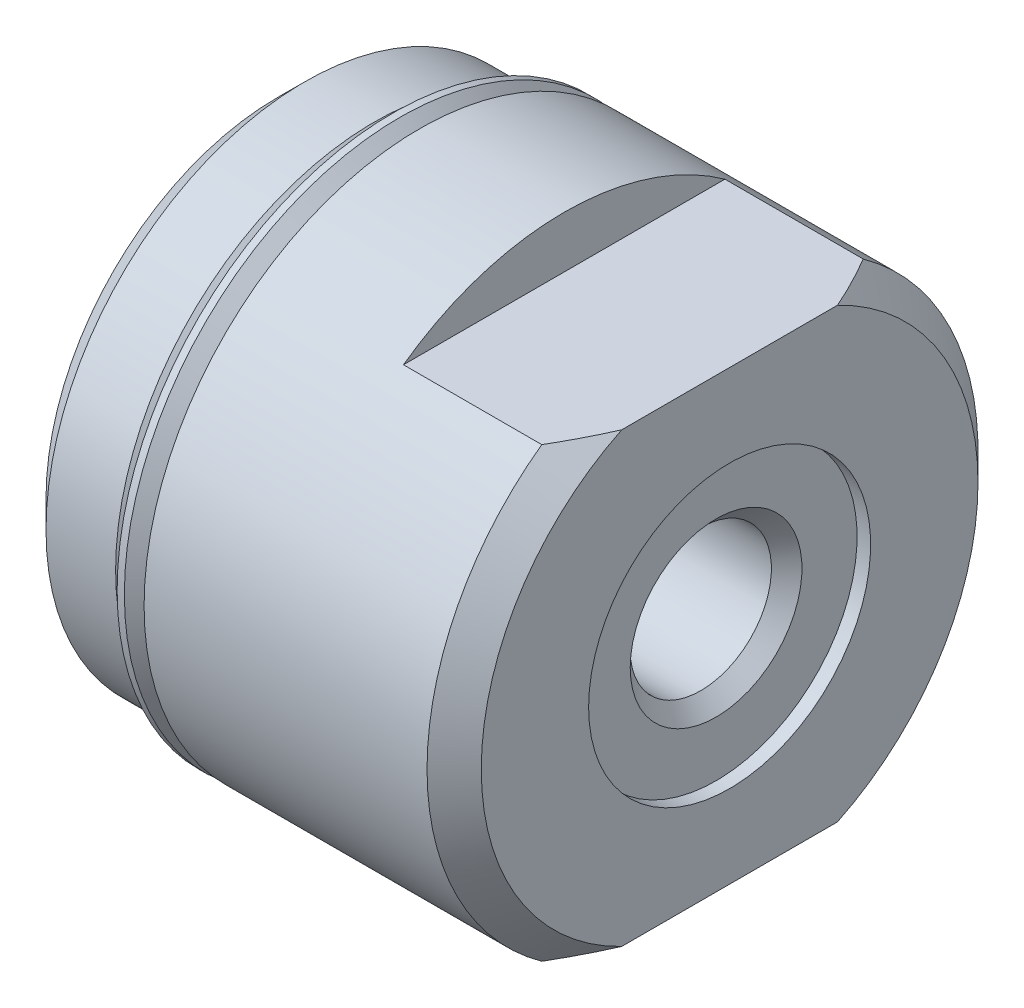
SolidWorks part; units mm, degrees
material "6061-T6 (SS)"
ref_plane "Front Plane" through (0, 0, 0) normal (0, 0, 1) x (1, 0, 0)
ref_plane "Top Plane" through (0, 0, 0) normal (0, 1, 0) x (1, 0, 0)
ref_plane "Right Plane" through (0, 0, 0) normal (1, 0, 0) x (0, 0, -1)
sketch "Sketch1" plane through (0, 0, 0) normal (0, 0, 1) x (1, 0, 0)
  line L0 (0, 0) -> (0, 6.5088)
  line L1 (0, 6.5088) -> (0.762, 7.2707)
  line L2 (0.762, 7.2707) -> (2.7178, 7.2707)
  line L3 (2.7178, 7.2707) -> (3.3528, 6.6357)
  line L4 (3.3528, 6.6357) -> (3.9878, 6.6357)
  line L5 (3.9878, 6.6357) -> (3.9878, 7.7406)
  line L6 (3.9878, 7.7406) -> (11.938, 7.7406)
  line L7 (11.938, 7.7406) -> (12.7, 6.9787)
  line L8 (12.7, 6.9787) -> (12.7, 0)
  line L9 (12.7, 0) -> (0, 0)
  line L10 (12.7, 0) -> (0, 0) construction
revolve "Revolve1" add sketch "Sketch1" angle 360 about L10 reverse direction yes
sketch "Sketch2" plane through (0, 0, 0) normal (0, 0, 1) x (1, 0, 0)
  line L0 (12.319, 0) -> (12.319, 3.9624)
  line L1 (12.319, 3.9624) -> (12.7, 3.9624)
  line L2 (12.7, 3.9624) -> (12.7, 0)
  line L3 (12.7, 0) -> (12.319, 0)
  line L4 (12.7, 0) -> (12.319, 0) construction
revolve "Cut-Revolve1" cut sketch "Sketch2" angle 360 about L4 reverse direction yes
sketch "Sketch3" plane through (0, 0, 0) normal (0, 0, 1) x (1, 0, 0)
  line L0 (0, 0) -> (0, 1.9837)
  line L1 (0, 1.9837) -> (11.8897, 1.9837)
  line L2 (11.8897, 1.9837) -> (12.319, 2.413)
  line L3 (12.319, 2.413) -> (12.319, 0)
  line L4 (12.319, 0) -> (0, 0)
  line L5 (12.319, 0) -> (0, 0) construction
revolve "Cut-Revolve2" cut sketch "Sketch3" angle 360 about L5 reverse direction yes
cosmetic thread "Cosmetic Thread1" parameters "D1"=5.08, "D2"=4.826
ref_plane "Plane1" through (12.7, 0, 0) normal (1, 0, 0) x (0, 0, -1)
sketch "Sketch4" plane through (12.7, 0, 0) normal (1, 0, 0) x (0, 0, -1)
  line L0 (-30.9626, -15.4813) -> (30.9626, -15.4813)
  line L1 (30.9626, -15.4813) -> (30.9626, 15.4813)
  line L2 (30.9626, 15.4813) -> (-30.9626, 15.4813)
  line L3 (-30.9626, 15.4813) -> (-30.9626, -15.4813)
  line L4 (-15.4813, -6.2865) -> (15.4813, -6.2865)
  line L5 (15.4813, -6.2865) -> (15.4813, 6.2865)
  line L6 (15.4813, 6.2865) -> (-15.4813, 6.2865)
  line L7 (-15.4813, 6.2865) -> (-15.4813, -6.2865)
extrude "Cut-Extrude1" cut sketch "Sketch4" against normal blind 4.6482
ref_plane "Plane2" through (13.5128, 0, 0) normal (1, 0, 0) x (0, 0, -1)
ref_plane "Plane3" through (0, 0, 0) normal (0, 0.9998, 0.0175) x (1, 0, 0)
ref_plane "Plane4" through (10.3124, 0, 0) normal (1, 0, 0) x (0, 0, -1)
ref_plane "Plane5" through (3.3528, 0, 0) normal (1, 0, 0) x (0, 0, -1)
sketch "Sketch5" plane through (0, 0, 0) normal (0, 0, 1) x (1, 0, 0)
  line L0 (3.2301, 7.7406) -> (3.2301, 7.6565)
  line L1 (3.2301, 7.6565) -> (3.8708, 7.0158)
  line L2 (3.8708, 6.8362) -> (3.6703, 6.6357)
  line L3 (3.6703, 6.6357) -> (3.3528, 6.6357)
  line L4 (3.3528, 6.6357) -> (3.3528, 6.3818)
  line L5 (3.3528, 6.3818) -> (3.9878, 6.3818)
  line L6 (3.9878, 6.3818) -> (3.9878, 7.1861)
  line L7 (3.9878, 7.1861) -> (3.4333, 7.7406)
  line L8 (3.4333, 7.7406) -> (3.2301, 7.7406)
  line L9 (3.9878, 0) -> (3.3528, 0) construction
  arc A0 (3.8708, 7.0158) -> (3.8708, 6.8362) centre (3.781, 6.926) cw
revolve "Revolve2" add sketch "Sketch5" angle 360 about L9 reverse direction yes
ref_plane "Plane6" through (12.827, 0, 0) normal (1, 0, 0) x (0, 0, -1)
ref_plane "Plane7" through (0, 0, 0) normal (1, 0, 0) x (0, 0, -1)
ref_plane "Plane8" through (8.0518, 0, 0) normal (1, 0, 0) x (0, 0, -1)
ref_plane "Plane9" through (12.7, 0, 0) normal (1, 0, 0) x (0, 0, -1)
ref_plane "Plane10" through (0, 0, 0) normal (0, 0, 1) x (1, 0, 0)
ref_plane "Plane11" through (0, 0, 0) normal (0, 1, 0) x (1, 0, 0)
ref_plane "Plane12" through (0, 0, 0) normal (0, 1, 0) x (1, 0, 0)
ref_plane "Plane13" through (13.5128, 0, 0) normal (1, 0, 0) x (0, 0, -1)
ref_plane "cut1 XY" through (12.7, 0, 0) normal (1, 0, 0) x (0, 0, -1)
ref_plane "cut1 XZ" through (0, 6.2865, 0) normal (0, -1, 0) x (-1, 0, 0)
ref_plane "cut1 YZ" through (0, 0, 0) normal (0, 0, -1) x (-1, 0, 0)
ref_axis "cut1 X" through (12.7, 6.2865, 80.9) along (0, 0, -1)
ref_axis "cut1 Y" through (12.7, -50, 0) along (0, 1, 0)
ref_axis "cut1 Z" through (80.9, 6.2865, 0) along (-1, 0, 0)
sketch3d "cut1"
  point P0 (12.7, 6.2865, 0)
ref_plane "cut2 XY" through (12.7, 0, 0) normal (1, 0, 0) x (0, 0, -1)
ref_plane "cut2 XZ" through (0, -6.2865, 0) normal (0, -1, 0) x (-1, 0, 0)
ref_plane "cut2 YZ" through (0, 0, 0) normal (0, 0, -1) x (-1, 0, 0)
ref_axis "cut2 X" through (12.7, -6.2865, 80.9) along (0, 0, -1)
ref_axis "cut2 Y" through (12.7, -50, 0) along (0, 1, 0)
ref_axis "cut2 Z" through (80.9, -6.2865, 0) along (-1, 0, 0)
sketch3d "cut2"
  point P0 (12.7, -6.2865, 0)
ref_plane "cutf1 XY" through (0, 0, 0) normal (0, 0, 1) x (1, 0, 0)
ref_plane "cutf1 XZ" through (0, 0, 0) normal (0, -1, 0) x (-1, 0, 0)
ref_plane "cutf1 YZ" through (12.7, 0, 0) normal (1, 0, 0) x (0, 0, -1)
ref_axis "cutf1 X" through (-80.9, 0, 0) along (1, 0, 0)
ref_axis "cutf1 Y" through (12.7, -50, 0) along (0, 1, 0)
ref_axis "cutf1 Z" through (12.7, 0, 80.9) along (0, 0, -1)
sketch3d "cutf1"
  point P0 (12.7, 0, 0)
ref_plane "cutf2 XY" through (0, 0, 0) normal (0, 0, 1) x (1, 0, 0)
ref_plane "cutf2 XZ" through (0, 0, 0) normal (0, -1, 0) x (-1, 0, 0)
ref_plane "cutf2 YZ" through (8.0518, 0, 0) normal (1, 0, 0) x (0, 0, -1)
ref_axis "cutf2 X" through (-80.9, 0, 0) along (1, 0, 0)
ref_axis "cutf2 Y" through (8.0518, -50, 0) along (0, 1, 0)
ref_axis "cutf2 Z" through (8.0518, 0, 80.9) along (0, 0, -1)
sketch3d "cutf2"
  point P0 (8.0518, 0, 0)
ref_plane "lovra XY" through (12.7, 0, 0) normal (1, 0, 0) x (0, 0, -1)
ref_plane "lovra XZ" through (0, 0, 0) normal (0, 0, -1) x (-1, 0, 0)
ref_plane "lovra YZ" through (0, 0, 0) normal (0, 1, 0) x (1, 0, 0)
ref_axis "lovra X" through (12.7, -50, 0) along (0, 1, 0)
ref_axis "lovra Y" through (12.7, 0, -80.9) along (0, 0, 1)
ref_axis "lovra Z" through (80.9, 0, 0) along (-1, 0, 0)
sketch3d "lovra"
  point P0 (12.7, 0, 0)
ref_plane "lovra1 XY" through (8.0518, 0, 0) normal (1, 0, 0) x (0, 0, -1)
ref_plane "lovra1 XZ" through (0, 0, 0) normal (0, -1, 0) x (-1, 0, 0)
ref_plane "lovra1 YZ" through (0, 0, 0) normal (0, 0, -1) x (-1, 0, 0)
ref_axis "lovra1 X" through (8.0518, 0, 80.9) along (0, 0, -1)
ref_axis "lovra1 Y" through (8.0518, -50, 0) along (0, 1, 0)
ref_axis "lovra1 Z" through (80.9, 0, 0) along (-1, 0, 0)
sketch3d "lovra1"
  point P0 (8.0518, 0, 0)
ref_plane "lovra2 XY" through (8.0518, 0, 0) normal (1, 0, 0) x (0, 0, -1)
ref_plane "lovra2 XZ" through (0, 6.2865, 0) normal (0, -1, 0) x (-1, 0, 0)
ref_plane "lovra2 YZ" through (0, 0, 0) normal (0, 0, -1) x (-1, 0, 0)
ref_axis "lovra2 X" through (8.0518, 6.2865, 80.9) along (0, 0, -1)
ref_axis "lovra2 Y" through (8.0518, -50, 0) along (0, 1, 0)
ref_axis "lovra2 Z" through (80.9, 6.2865, 0) along (-1, 0, 0)
sketch3d "lovra2"
  point P0 (8.0518, 6.2865, 0)
ref_plane "lovra21 XY" through (0, 0, 0) normal (1, 0, 0) x (0, 0, -1)
ref_plane "lovra21 XZ" through (0, 0, 0) normal (0, -1, 0) x (-1, 0, 0)
ref_plane "lovra21 YZ" through (0, 0, 5.2705) normal (0, 0, -1) x (-1, 0, 0)
ref_axis "lovra21 X" through (0, 0, 80.9) along (0, 0, -1)
ref_axis "lovra21 Y" through (0, -50, 5.2705) along (0, 1, 0)
ref_axis "lovra21 Z" through (80.9, 0, 5.2705) along (-1, 0, 0)
sketch3d "lovra21"
  point P0 (0, 0, 5.2705)
ref_plane "lovra22 XY" through (0, 0, 0) normal (1, 0, 0) x (0, 0, -1)
ref_plane "lovra22 XZ" through (0, 0, 0) normal (0, -1, 0) x (-1, 0, 0)
ref_plane "lovra22 YZ" through (0, 0, -5.2705) normal (0, 0, -1) x (-1, 0, 0)
ref_axis "lovra22 X" through (0, 0, 80.9) along (0, 0, -1)
ref_axis "lovra22 Y" through (0, -50, -5.2705) along (0, 1, 0)
ref_axis "lovra22 Z" through (80.9, 0, -5.2705) along (-1, 0, 0)
sketch3d "lovra22"
  point P0 (0, 0, -5.2705)
ref_plane "lovra3 XY" through (8.0518, 0, 0) normal (1, 0, 0) x (0, 0, -1)
ref_plane "lovra3 XZ" through (0, -6.2865, 0) normal (0, -1, 0) x (-1, 0, 0)
ref_plane "lovra3 YZ" through (0, 0, 0) normal (0, 0, -1) x (-1, 0, 0)
ref_axis "lovra3 X" through (8.0518, -6.2865, 80.9) along (0, 0, -1)
ref_axis "lovra3 Y" through (8.0518, -50, 0) along (0, 1, 0)
ref_axis "lovra3 Z" through (80.9, -6.2865, 0) along (-1, 0, 0)
sketch3d "lovra3"
  point P0 (8.0518, -6.2865, 0)
ref_plane "olen XY" through (12.7, 0, 0) normal (1, 0, 0) x (0, 0, -1)
ref_plane "olen XZ" through (0, 0, 0) normal (0, -1, 0) x (-1, 0, 0)
ref_plane "olen YZ" through (0, 0, 0) normal (0, 0, -1) x (-1, 0, 0)
ref_axis "olen X" through (12.7, 0, 80.9) along (0, 0, -1)
ref_axis "olen Y" through (12.7, -50, 0) along (0, 1, 0)
ref_axis "olen Z" through (80.9, 0, 0) along (-1, 0, 0)
sketch3d "olen"
  point P0 (12.7, 0, 0)
ref_plane "to_mounting_bracket XY" through (13.5128, 0, 0) normal (1, 0, 0) x (0, 0, -1)
ref_plane "to_mounting_bracket XZ" through (0, 0, 0) normal (0, -1, 0) x (-1, 0, 0)
ref_plane "to_mounting_bracket YZ" through (0, 0, 0) normal (0, 0, -1) x (-1, 0, 0)
ref_axis "to_mounting_bracket X" through (13.5128, 0, 80.9) along (0, 0, -1)
ref_axis "to_mounting_bracket Y" through (13.5128, -50, 0) along (0, 1, 0)
ref_axis "to_mounting_bracket Z" through (80.9, 0, 0) along (-1, 0, 0)
sketch3d "to_mounting_bracket"
  point P0 (13.5128, 0, 0)
ref_plane "to_nut XY" through (0, 0, 0) normal (1, 0, 0) x (0, 0, -1)
ref_plane "to_nut XZ" through (0, 0, 0) normal (0, -1, 0) x (-1, 0, 0)
ref_plane "to_nut YZ" through (0, 0, 0) normal (0, 0, -1) x (-1, 0, 0)
ref_axis "to_nut X" through (0, 0, 80.9) along (0, 0, -1)
ref_axis "to_nut Y" through (0, -50, 0) along (0, 1, 0)
ref_axis "to_nut Z" through (80.9, 0, 0) along (-1, 0, 0)
sketch3d "to_nut"
  point P0 (0, 0, 0)
ref_plane "to_pin XY" through (0, 0, 0) normal (0, 0, 1) x (1, 0, 0)
ref_plane "to_pin XZ" through (0, 0, 0) normal (0, -1, 0) x (-1, 0, 0)
ref_plane "to_pin YZ" through (19.8374, 0, 0) normal (1, 0, 0) x (0, 0, -1)
ref_axis "to_pin X" through (-80.9, 0, 0) along (1, 0, 0)
ref_axis "to_pin Y" through (19.8374, -50, 0) along (0, 1, 0)
ref_axis "to_pin Z" through (19.8374, 0, 80.9) along (0, 0, -1)
sketch3d "to_pin"
  point P0 (19.8374, 0, 0)
ref_plane "to_screw XY" through (0, 0, 0) normal (0, 1, 0) x (1, 0, 0)
ref_plane "to_screw XZ" through (0, 0, 0) normal (0, 0, 1) x (1, 0, 0)
ref_plane "to_screw YZ" through (10.3124, 0, 0) normal (1, 0, 0) x (0, 0, -1)
ref_axis "to_screw X" through (-80.9, 0, 0) along (1, 0, 0)
ref_axis "to_screw Y" through (10.3124, 0, 50) along (0, 0, -1)
ref_axis "to_screw Z" through (10.3124, 50, 0) along (0, -1, 0)
sketch3d "to_screw"
  point P0 (10.3124, 0, 0)
ref_plane "to_tube XY" through (3.3528, 0, 0) normal (1, 0, 0) x (0, 0, -1)
ref_plane "to_tube XZ" through (0, 0, 0) normal (0, -1, 0) x (-1, 0, 0)
ref_plane "to_tube YZ" through (0, 0, 0) normal (0, 0, -1) x (-1, 0, 0)
ref_axis "to_tube X" through (3.3528, 0, 80.9) along (0, 0, -1)
ref_axis "to_tube Y" through (3.3528, -50, 0) along (0, 1, 0)
ref_axis "to_tube Z" through (80.9, 0, 0) along (-1, 0, 0)
sketch3d "to_tube"
  point P0 (3.3528, 0, 0)
